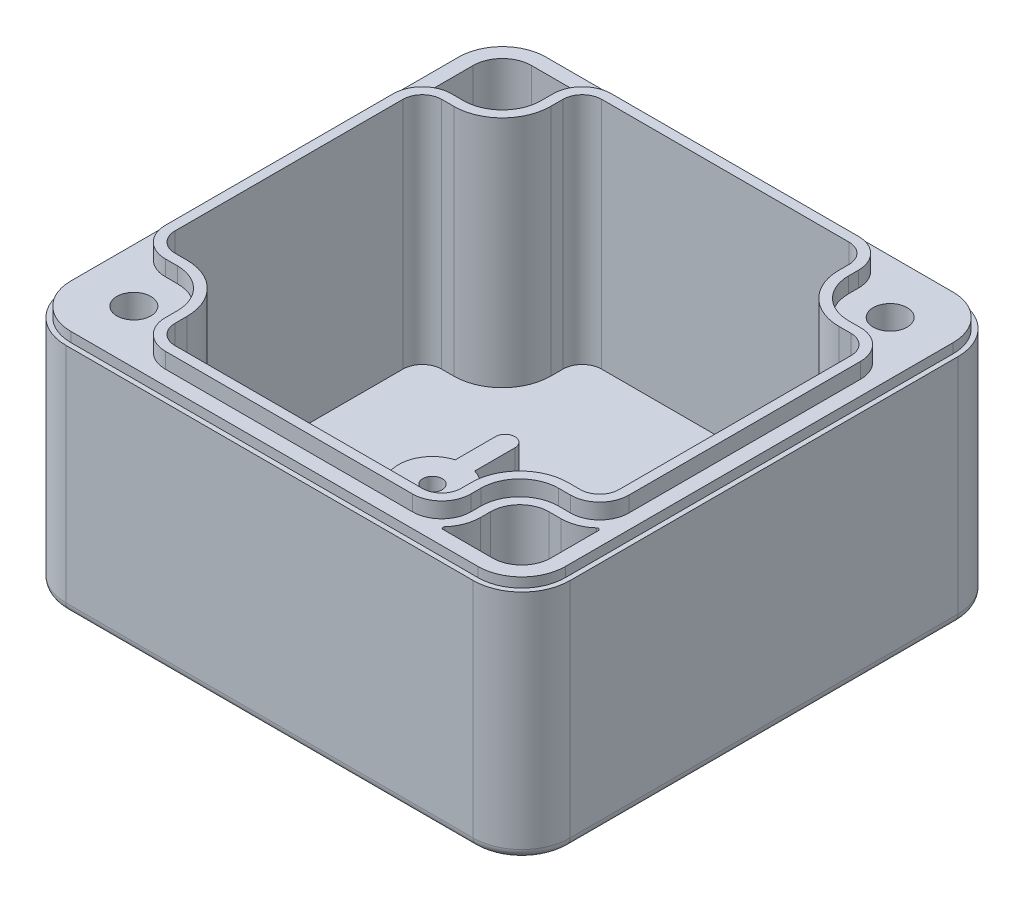
SolidWorks part; units mm, degrees
ref_plane "Спереди" through (0, 0, 0) normal (0, 0, 1) x (1, 0, 0)
ref_plane "Сверху" through (0, 0, 0) normal (0, 1, 0) x (1, 0, 0)
ref_plane "Справа" through (0, 0, 0) normal (1, 0, 0) x (0, 0, -1)
sketch "Эскиз1" plane through (0, 0, 0) normal (0, 1, 0) x (1, 0, 0)
  line L1 (-21, 25) -> (21, 25)
  line L2 (-26, 20) -> (-26, -20)
  line L3 (-21, -25) -> (21, -25)
  line L4 (26, 20) -> (26, -20)
  line L5 (-26, 25) -> (26, -25) construction
  line L6 (-26, -25) -> (26, 25) construction
  arc A0 (21, 25) -> (26, 20) centre (21, 20) cw
  arc A1 (26, -20) -> (21, -25) centre (21, -20) cw
  arc A2 (-21, -25) -> (-26, -20) centre (-21, -20) cw
  arc A3 (-26, 20) -> (-21, 25) centre (-21, 20) cw
  point P0 (0, 0)
  dimension "D3" = 5
  dimension "D1" = 52
  dimension "D2" = 50
sketch "Эскиз2" plane through (0, 0, 0) normal (0, 1, 0) x (1, 0, 0)
  line L0 (-14.75, 20) -> (-14.75, 18.75)
  line L1 (-19.75, 13.75) -> (-21, 13.75)
  line L2 (-23, 11.75) -> (-23, -11.75)
  line L3 (-21, -13.75) -> (-19.75, -13.75)
  line L4 (-14.75, -18.75) -> (-14.75, -20)
  line L5 (-12.75, -22) -> (12.75, -22)
  line L6 (14.75, -20) -> (14.75, -18.9552)
  line L7 (19.75, -13.9552) -> (21, -13.9552)
  line L8 (23, -11.9552) -> (23, 11.9552)
  line L9 (21, 13.9552) -> (19.75, 13.9552)
  line L10 (14.75, 18.9552) -> (14.75, 20)
  line L11 (12.75, 22) -> (-12.75, 22)
  line L12 (-21, 25) -> (21, 25) construction
  line L13 (-21, -25) -> (21, -25) construction
  line L14 (-26, 20) -> (-26, -20) construction
  line L15 (26, 20) -> (26, -20) construction
  arc A0 (-14.75, 20) -> (-12.75, 22) centre (-12.75, 20) cw
  arc A1 (14.75, 20) -> (12.75, 22) centre (12.75, 20) ccw
  arc A2 (23, 11.9552) -> (21, 13.9552) centre (21, 11.9552) ccw
  arc A3 (23, -11.9552) -> (21, -13.9552) centre (21, -11.9552) cw
  arc A4 (14.75, -20) -> (12.75, -22) centre (12.75, -20) cw
  arc A5 (-12.75, -22) -> (-14.75, -20) centre (-12.75, -20) cw
  arc A6 (-21, -13.75) -> (-23, -11.75) centre (-21, -11.75) cw
  arc A7 (-23, 11.75) -> (-21, 13.75) centre (-21, 11.75) cw
  arc A8 (-19.75, -13.75) -> (-14.75, -18.75) centre (-19.75, -18.75) cw
  arc A9 (14.75, -18.9552) -> (19.75, -13.9552) centre (19.75, -18.9552) cw
  arc A10 (19.75, 13.9552) -> (14.75, 18.9552) centre (19.75, 18.9552) cw
  arc A11 (-19.75, 13.75) -> (-14.75, 18.75) centre (-19.75, 18.75) ccw
  point P3 (0, 22)
  point P13 (-23, 0)
  point P14 (0, -22)
  point P15 (23, 0)
  dimension "D7" = 2
  dimension "D8" = 5
  dimension "D1" = 3
  dimension "D2" = 3
  dimension "D3" = 3
  dimension "D4" = 3
  dimension "D5" = 29.5
  dimension "D6" = 27.5
extrude "Бобышка-Вытянуть1" add sketch "Эскиз1" along normal blind 25
extrude "Вырез-Вытянуть1" cut sketch "Эскиз2" along normal up to surface (25 mm away) from offset 2.5 up to face at (0, 25, 0)
sketch "Эскиз4" plane through (0, 0, 0) normal (0, 1, 0) x (1, 0, 0)
  line L8 (-25.5, 20) -> (-25.5, -20)
  line L9 (-21, -24.5) -> (21, -24.5)
  line L10 (25.5, -20) -> (25.5, 20)
  line L11 (21, 24.5) -> (-21, 24.5)
  line L12 (-25.5, 20) -> (-25.5, -20)
  line L13 (-21, -24.5) -> (21, -24.5)
  line L14 (25.5, -20) -> (25.5, 20)
  line L15 (21, 24.5) -> (-21, 24.5)
  arc A8 (-25.5, -20) -> (-21, -24.5) centre (-21, -20) ccw
  arc A9 (21, -24.5) -> (25.5, -20) centre (21, -20) ccw
  arc A10 (25.5, 20) -> (21, 24.5) centre (21, 20) ccw
  arc A11 (-21, 24.5) -> (-25.5, 20) centre (-21, 20) ccw
  arc A12 (-25.5, -20) -> (-21, -24.5) centre (-21, -20) ccw
  arc A13 (21, -24.5) -> (25.5, -20) centre (21, -20) ccw
  arc A14 (25.5, 20) -> (21, 24.5) centre (21, 20) ccw
  arc A15 (-21, 24.5) -> (-25.5, 20) centre (-21, 20) ccw
  dimension "D1" = 0.5
sketch "Эскиз5" plane through (0, 0, 0) normal (0, 1, 0) x (1, 0, 0)
  line L24 (-16.75, 20) -> (-16.75, 18.75)
  line L25 (-19.75, 15.75) -> (-21, 15.75)
  line L26 (-25, 11.75) -> (-25, -11.75)
  line L27 (-21, -15.75) -> (-19.75, -15.75)
  line L28 (-16.75, -18.75) -> (-16.75, -20)
  line L29 (-12.75, -24) -> (12.75, -24)
  line L30 (16.75, -20) -> (16.75, -18.9552)
  line L31 (19.75, -15.9552) -> (21, -15.9552)
  line L32 (25, -11.9552) -> (25, 11.9552)
  line L33 (21, 15.9552) -> (19.75, 15.9552)
  line L34 (16.75, 18.9552) -> (16.75, 20)
  line L35 (12.75, 24) -> (-12.75, 24)
  line L36 (-16.75, 20) -> (-16.75, 18.75)
  line L37 (-19.75, 15.75) -> (-21, 15.75)
  line L38 (-25, 11.75) -> (-25, -11.75)
  line L39 (-21, -15.75) -> (-19.75, -15.75)
  line L40 (-16.75, -18.75) -> (-16.75, -20)
  line L41 (-12.75, -24) -> (12.75, -24)
  line L42 (16.75, -20) -> (16.75, -18.9552)
  line L43 (19.75, -15.9552) -> (21, -15.9552)
  line L44 (25, -11.9552) -> (25, 11.9552)
  line L45 (21, 15.9552) -> (19.75, 15.9552)
  line L46 (16.75, 18.9552) -> (16.75, 20)
  line L47 (12.75, 24) -> (-12.75, 24)
  arc A24 (-19.75, 15.75) -> (-16.75, 18.75) centre (-19.75, 18.75) ccw
  arc A25 (-21, 15.75) -> (-25, 11.75) centre (-21, 11.75) ccw
  arc A26 (-25, -11.75) -> (-21, -15.75) centre (-21, -11.75) ccw
  arc A27 (-16.75, -18.75) -> (-19.75, -15.75) centre (-19.75, -18.75) ccw
  arc A28 (-16.75, -20) -> (-12.75, -24) centre (-12.75, -20) ccw
  arc A29 (12.75, -24) -> (16.75, -20) centre (12.75, -20) ccw
  arc A30 (19.75, -15.9552) -> (16.75, -18.9552) centre (19.75, -18.9552) ccw
  arc A31 (21, -15.9552) -> (25, -11.9552) centre (21, -11.9552) ccw
  arc A32 (25, 11.9552) -> (21, 15.9552) centre (21, 11.9552) ccw
  arc A33 (16.75, 18.9552) -> (19.75, 15.9552) centre (19.75, 18.9552) ccw
  arc A34 (16.75, 20) -> (12.75, 24) centre (12.75, 20) ccw
  arc A35 (-12.75, 24) -> (-16.75, 20) centre (-12.75, 20) ccw
  arc A36 (-19.75, 15.75) -> (-16.75, 18.75) centre (-19.75, 18.75) ccw
  arc A37 (-21, 15.75) -> (-25, 11.75) centre (-21, 11.75) ccw
  arc A38 (-25, -11.75) -> (-21, -15.75) centre (-21, -11.75) ccw
  arc A39 (-16.75, -18.75) -> (-19.75, -15.75) centre (-19.75, -18.75) ccw
  arc A40 (-16.75, -20) -> (-12.75, -24) centre (-12.75, -20) ccw
  arc A41 (12.75, -24) -> (16.75, -20) centre (12.75, -20) ccw
  arc A42 (19.75, -15.9552) -> (16.75, -18.9552) centre (19.75, -18.9552) ccw
  arc A43 (21, -15.9552) -> (25, -11.9552) centre (21, -11.9552) ccw
  arc A44 (25, 11.9552) -> (21, 15.9552) centre (21, 11.9552) ccw
  arc A45 (16.75, 18.9552) -> (19.75, 15.9552) centre (19.75, 18.9552) ccw
  arc A46 (16.75, 20) -> (12.75, 24) centre (12.75, 20) ccw
  arc A47 (-12.75, 24) -> (-16.75, 20) centre (-12.75, 20) ccw
  dimension "D1" = 2
sketch "Эскиз6" plane through (0, 0, 0) normal (0, 1, 0) x (1, 0, 0)
  line L8 (-24, 20) -> (-24, -20)
  line L9 (-21, -23) -> (21, -23)
  line L10 (24, -20) -> (24, 20)
  line L11 (21, 23) -> (-21, 23)
  line L12 (-24, 20) -> (-24, -20)
  line L13 (-21, -23) -> (21, -23)
  line L14 (24, -20) -> (24, 20)
  line L15 (21, 23) -> (-21, 23)
  arc A8 (-21, 23) -> (-24, 20) centre (-21, 20) ccw
  arc A9 (-24, -20) -> (-21, -23) centre (-21, -20) ccw
  arc A10 (21, -23) -> (24, -20) centre (21, -20) ccw
  arc A11 (24, 20) -> (21, 23) centre (21, 20) ccw
  arc A12 (-21, 23) -> (-24, 20) centre (-21, 20) ccw
  arc A13 (-24, -20) -> (-21, -23) centre (-21, -20) ccw
  arc A14 (21, -23) -> (24, -20) centre (21, -20) ccw
  arc A15 (24, 20) -> (21, 23) centre (21, 20) ccw
  dimension "D1" = 2
sketch "Эскиз8" plane through (0, 0, 0) normal (0, 1, 0) x (1, 0, 0)
  line L0 (-24, 20) -> (-24, -20) construction
  line L1 (21, 23) -> (-21, 23) construction
  line L2 (-16.75, 20) -> (-16.75, 18.75) construction
  line L3 (-19.75, 15.75) -> (-21, 15.75) construction
  line L4 (-24, 20) -> (-24, 14.3958)
  line L5 (-15.3958, 23) -> (-21, 23)
  line L6 (-16.75, 20) -> (-16.75, 18.75)
  line L7 (-19.75, 15.75) -> (-21, 15.75)
  line L8 (19.75, -15.9552) -> (21, -15.9552) construction
  line L9 (16.75, -20) -> (16.75, -18.9552) construction
  line L10 (-21, -23) -> (21, -23) construction
  line L11 (24, -20) -> (24, 20) construction
  line L12 (19.75, -15.9552) -> (21, -15.9552)
  line L13 (16.75, -20) -> (16.75, -18.9552)
  line L14 (15.3958, -23) -> (21, -23)
  line L15 (24, -20) -> (24, -14.6009)
  arc A0 (-21, 23) -> (-24, 20) centre (-21, 20) ccw construction
  arc A1 (-12.75, 24) -> (-16.75, 20) centre (-12.75, 20) ccw construction
  arc A2 (-19.75, 15.75) -> (-16.75, 18.75) centre (-19.75, 18.75) ccw construction
  arc A3 (-21, 15.75) -> (-25, 11.75) centre (-21, 11.75) ccw construction
  arc A4 (-21, 23) -> (-24, 20) centre (-21, 20) ccw
  arc A5 (-15.3958, 23) -> (-16.75, 20) centre (-12.75, 20) ccw
  arc A6 (-19.75, 15.75) -> (-16.75, 18.75) centre (-19.75, 18.75) ccw
  arc A7 (-21, 15.75) -> (-24, 14.3958) centre (-21, 11.75) ccw
  arc A8 (21, -15.9552) -> (25, -11.9552) centre (21, -11.9552) ccw construction
  arc A9 (19.75, -15.9552) -> (16.75, -18.9552) centre (19.75, -18.9552) ccw construction
  arc A10 (12.75, -24) -> (16.75, -20) centre (12.75, -20) ccw construction
  arc A11 (21, -23) -> (24, -20) centre (21, -20) ccw construction
  arc A12 (21, -15.9552) -> (24, -14.6009) centre (21, -11.9552) ccw
  arc A13 (19.75, -15.9552) -> (16.75, -18.9552) centre (19.75, -18.9552) ccw
  arc A14 (15.3958, -23) -> (16.75, -20) centre (12.75, -20) ccw
  arc A15 (21, -23) -> (24, -20) centre (21, -20) ccw
extrude "Вырез-Вытянуть3" cut sketch "Эскиз8" along normal up to surface (25 mm away) from offset 3 up to face at (0, 25, 0)
extrude "Вытянуть-Тонкостенный1" add sketch "Эскиз2<2>" along normal blind 1.6 from surface thin contours L11 A0 L0 A11 L1 A7 L2 A6 L3 A8 L4 A5 L5 A4 L6 A9 L7 A3 L8 A2 L9 A10 L10 A1 starting at face at (-19.8893, 25, -18.8893) thin type one direction wall 1
sketch "Эскиз2<2>" plane through (0, 0, 0) normal (0, 1, 0) x (1, 0, 0) same geometry as "Эскиз2"
extrude "Вырез-Вытянуть-Тонкостенный1" cut sketch "Эскиз4" against normal blind 1 from offset 25 thin contours A15 L12 A12 L13 A13 L14 A14 L15 thin type one direction wall 1
fillet "Скругление1" radius 0.2 4 edges at (24, 14, 14.6009) (15.3958, 14, 23) (-24, 14, -14.3958) (-15.3958, 14, -23)
sketch "Эскиз9" plane through (0, 0, 0) normal (0, 1, 0) x (1, 0, 0)
  line L1 (-20, 19) -> (20, 19) construction
  line L2 (-20, 19) -> (-20, -19) construction
  line L3 (-20, -19) -> (20, -19) construction
  line L4 (20, 19) -> (20, -19) construction
  line L5 (-20, 19) -> (20, -19) construction
  line L6 (-20, -19) -> (20, 19) construction
  circle A0 centre (-20, 19) radius 2.25
  circle A1 centre (20, -19) radius 2.25
  point P0 (0, 0)
  dimension "D3" = 4.5
  dimension "D1" = 40
  dimension "D2" = 38
extrude "Вырез-Вытянуть4" cut sketch "Эскиз9" along normal blind 4
sketch "Эскиз10" plane through (0, 0, 0) normal (0, 1, 0) x (1, 0, 0)
  circle A0 centre (20, 19) radius 4
  circle A1 centre (-20, -19) radius 4
  dimension "D1" = 8
extrude "Вырез-Вытянуть5" cut sketch "Эскиз10" along normal blind 17
fillet "Скругление2" radius 1 8 edges at (24.5355, 0, -23.5355) (26, 0, 0) (24.5355, 0, 23.5355) (0, 0, 25) (-24.5355, 0, 23.5355) (-26, 0, 0) (-24.5355, 0, -23.5355) (0, 0, -25)
sketch "Эскиз11" plane through (0, 0, 0) normal (0, 1, 0) x (1, 0, 0)
  circle A0 centre (-20, -19) radius 1.75
  circle A1 centre (20, 19) radius 1.75
  dimension "D1" = 3.5
extrude "Вырез-Вытянуть6" cut sketch "Эскиз11" along normal up to surface (25 mm away) up to face at (19.8809, 25, 18.9835)
sketch "Эскиз12" plane through (0, 0, 0) normal (0, 1, 0) x (1, 0, 0)
  line L0 (-8.2, 7.5) -> (-8.2, -7.5) construction
  line L1 (-7.2, 7.5) -> (-7.2, -7.5)
  line L2 (-9.2, 7.5) -> (-9.2, -7.5)
  arc A0 (-7.2, 7.5) -> (-9.2, 7.5) centre (-8.2, 7.5) ccw
  arc A1 (-9.2, -7.5) -> (-7.2, -7.5) centre (-8.2, -7.5) ccw
  point P2 (-8.2, 0)
  point P7 (-8.2, 8.5)
  point P8 (-8.2, -8.5)
  dimension "D1" = 2
  dimension "D2" = 17
  dimension "D3" = 8.2
extrude "Бобышка-Вытянуть2" add sketch "Эскиз12" along normal blind 5.5
sketch "Эскиз13" plane through (0, 0, 0) normal (0, 1, 0) x (1, 0, 0)
  circle A0 centre (-8.2, 0) radius 3.5
  dimension "D1" = 7
extrude "Бобышка-Вытянуть3" add sketch "Эскиз13" along normal blind 5.5
sketch "Эскиз14" plane through (0, 5.5, 0) normal (0, 1, 0) x (1, 0, 0)
  circle A0 centre (-8.2, 0) radius 1
  dimension "D1" = 2
extrude "Вырез-Вытянуть7" cut sketch "Эскиз14" against normal offset from surface (4.5 mm away) 1 up to face at (0, 0, 0)
mirror "Зеркальное отражение1" about plane through (0, 0, 0) normal (1, 0, 0) of "Вырез-Вытянуть7", "Бобышка-Вытянуть2", "Бобышка-Вытянуть3"
